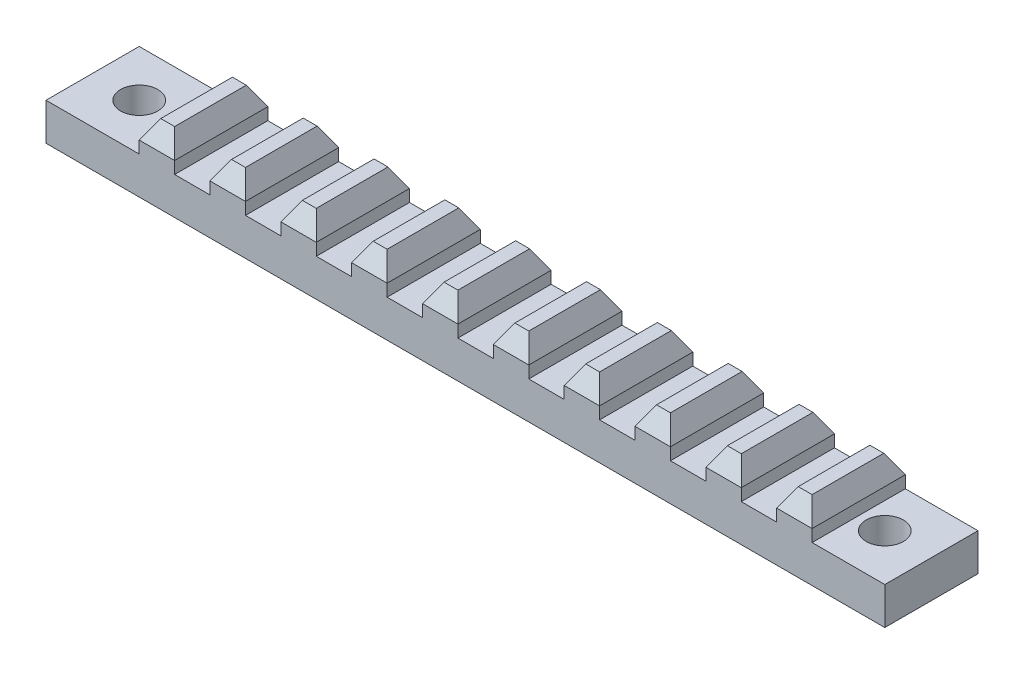
SolidWorks part; units mm, degrees
ref_plane "Front Plane" through (0, 0, 0) normal (0, 0, 1) x (1, 0, 0)
ref_plane "Top Plane" through (0, 0, 0) normal (0, 1, 0) x (1, 0, 0)
ref_plane "Right Plane" through (0, 0, 0) normal (1, 0, 0) x (0, 0, -1)
sketch "Sketch1" plane through (0, 0, 0) normal (0, 1, 0) x (1, 0, 0)
  line L0 (1.5, -2.5) -> (0, -2.5) construction
  line L1 (0, 0) -> (45, 0)
  line L2 (0, 0) -> (0, -5)
  line L3 (0, -5) -> (45, -5)
  line L4 (45, 0) -> (45, -5)
  line L5 (43.5, -2.5) -> (45, -2.5) construction
  circle A0 centre (2.5, -2.5) radius 1
  circle A1 centre (42.5, -2.5) radius 1
  dimension "D3" = 2
  dimension "D1" = 5
  dimension "D2" = 45
  dimension "D4" = 1.5
extrude "Boss-Extrude1" add sketch "Sketch1" along normal blind 2
sketch "Sketch2" plane through (0, 0, 5) normal (0, 0, 1) x (1, 0, 0)
  line L0 (5, 2) -> (5, 3.65)
  line L2 (0, 2) -> (45, 2) construction
  line L3 (5, 3.65) -> (6.9, 3.65)
  line L4 (6.9, 3.65) -> (6.9, 2)
  line L9 (0, 0) -> (45, 0)
  line L10 (45, 0) -> (45, 2)
  line L11 (45, 2) -> (0, 2)
  line L12 (0, 2) -> (0, 0)
  line L15 (6.9, 2) -> (5, 2)
  dimension "D1" = 1.9
  dimension "D2" = 1.65
  dimension "D3" = 5
  dimension "D4" = 0
extrude "Boss-Extrude2" add sketch "Sketch2" against normal up to surface (5 mm away) up to face at (22.5, 1, 0)
chamfer "Chamfer1" distance 1 angle 30 4 edges at (5.95, 3.65, 0) (6.9, 3.65, 2.5) (5.95, 3.65, 5) (5, 3.65, 2.5) first distance on face at (16.9187, 1.9125, 0) first distance on face at (6.9, 2.825, 1.875) first distance on face at (11.5312, 1.9125, 5) first distance on face at (5, 2.825, 1.875)
pattern_linear "LPattern1" count 10 spacing 3.8 along (1, 0, 0) of "Boss-Extrude2", "Chamfer1"
